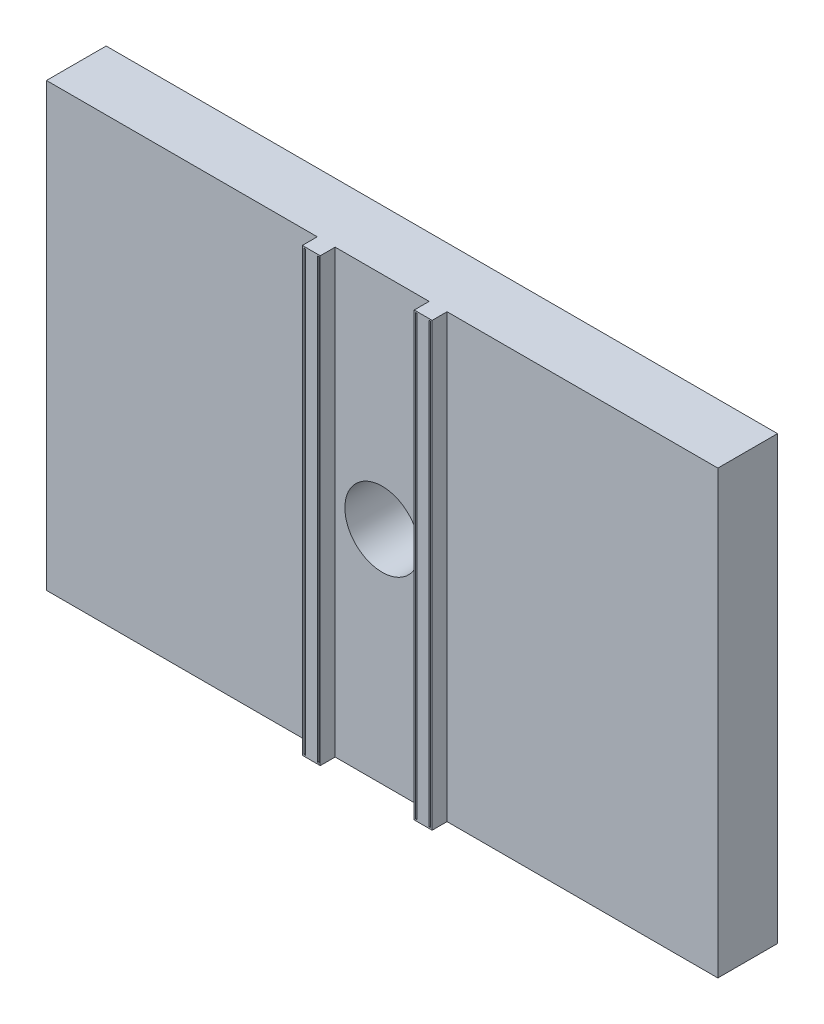
SolidWorks part; units mm, degrees
material "1060 Alloy"
ref_plane "Front Plane" through (0, 0, 0) normal (0, 0, 1) x (1, 0, 0)
ref_plane "Top Plane" through (0, 0, 0) normal (0, 1, 0) x (1, 0, 0)
ref_plane "Right Plane" through (0, 0, 0) normal (1, 0, 0) x (0, 0, -1)
sketch "Sketch1" plane through (0, 0, 0) normal (0, 0, 1) x (1, 0, 0)
  line L1 (-28.0987, 37.592) -> (29.0513, 37.592)
  line L2 (-28.0987, 37.592) -> (-28.0987, 0)
  line L3 (-28.0987, 0) -> (29.0513, 0)
  line L4 (29.0513, 37.592) -> (29.0513, 0)
  dimension "D1" = 57.15
  dimension "D2" = 37.592
extrude "Boss-Extrude1" add sketch "Sketch1" along normal blind 10.16
sketch "Sketch2" plane through (0, 0, 10.16) normal (0, 0, 1) x (1, 0, 0)
  line L0 (-20.0977, 37.592) -> (-19.8437, 37.592)
  line L1 (29.0513, 37.592) -> (-28.0987, 37.592) construction
  line L3 (-20.0977, 37.592) -> (-20.0977, 0)
  line L4 (-28.0987, 0) -> (29.0513, 0) construction
  line L5 (-19.8437, 37.592) -> (-19.8437, 0)
  line L6 (-19.8437, 0) -> (-20.0977, 0)
  line L7 (-17.5577, 37.592) -> (-17.5577, 0)
  line L8 (-19.5897, 37.592) -> (-17.5577, 37.592)
  line L9 (-19.5897, 37.592) -> (-19.5897, 0)
  line L10 (-19.5897, 0) -> (-17.5577, 0)
  line L12 (-17.3037, 37.592) -> (-17.0497, 37.592)
  line L13 (-17.3037, 37.592) -> (-17.3037, 0)
  line L14 (-17.0497, 37.592) -> (-17.0497, 0)
  line L15 (-17.0497, 0) -> (-17.3037, 0)
  dimension "D2" = 0.254
  dimension "D3" = 0.254
  dimension "D4" = 2.032
  dimension "D5" = 0.254
  dimension "D6" = 0.254
extrude "Boss-Extrude2" add sketch "Sketch2" along normal blind 2.54
sketch "Sketch3" plane through (0, 0, 10.16) normal (0, 0, 1) x (1, 0, 0)
  circle A0 centre (-28.0987, 0) radius 6.35
extrude "Cut-Extrude1" cut sketch "Sketch3" against normal blind 21.082
sketch "Sketch4" plane through (0, 0, 0) normal (0, 0, -1) x (-1, 0, 0)
  circle A0 centre (12.0044, 16.0943) radius 2.032
  dimension "D4" = 4.064
extrude "Cut-Extrude2" cut sketch "Sketch4" against normal blind 5.08
sketch "Sketch5" plane through (-20.0977, 0, 0) normal (-1, 0, 0) x (0, 0, 1)
  line L0 (10.16, 37.592) -> (12.7, 37.592)
  line L1 (12.7, 37.592) -> (12.7, 37.338)
  line L2 (12.7, 37.592) -> (12.7, 0) construction
  line L3 (12.7, 37.338) -> (10.16, 37.338)
  line L4 (10.16, 37.592) -> (10.16, 6.35) construction
  line L5 (10.16, 37.338) -> (10.16, 37.592)
  dimension "D1" = 0.254
extrude "Boss-Extrude3" add sketch "Sketch5" against normal blind 3.048
mirror "Mirror1" about plane through (-28.0987, 37.592, 10.16) normal (1, 0, 0) of "Boss-Extrude3", "Cut-Extrude2", "Cut-Extrude1", "Boss-Extrude2", "Boss-Extrude1"
mirror "Mirror2" about plane through (0, 0, 0) normal (0, 1, 0) of "Mirror1", "Boss-Extrude3", "Cut-Extrude2", "Cut-Extrude1", "Boss-Extrude2", "Boss-Extrude1"
